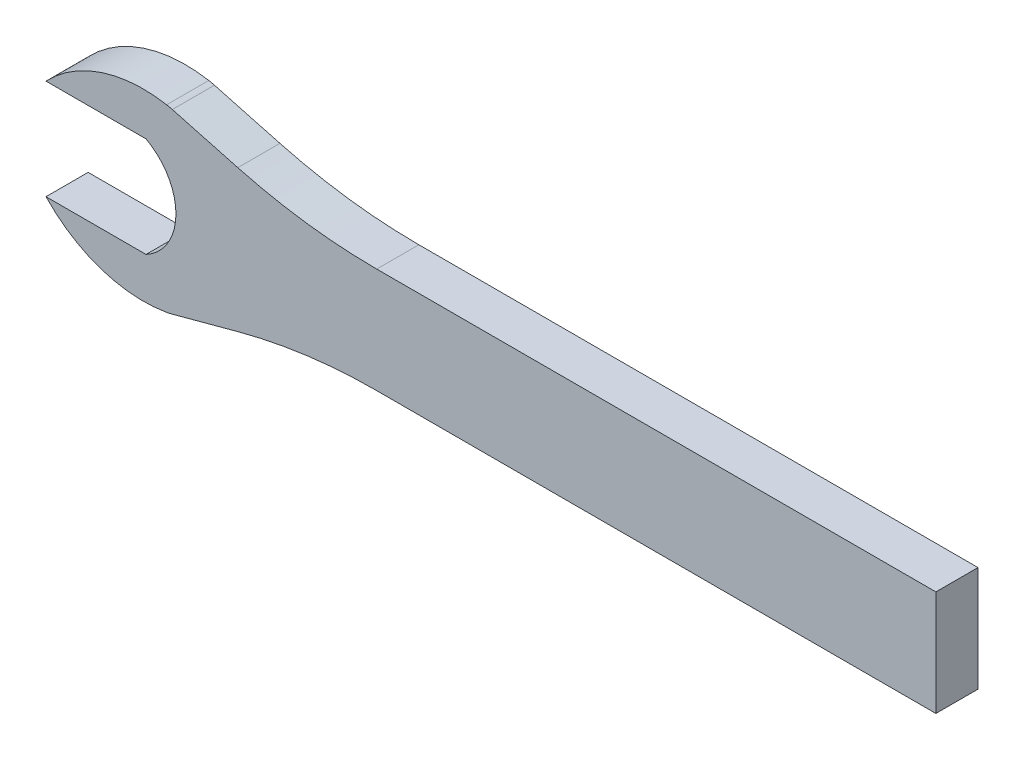
SolidWorks part; units mm, degrees
material "주조 탄소강"
ref_plane "Front Plane" through (0, 0, 0) normal (0, 0, 1) x (1, 0, 0)
ref_plane "Top Plane" through (0, 0, 0) normal (0, 1, 0) x (1, 0, 0)
ref_plane "Right Plane" through (0, 0, 0) normal (1, 0, 0) x (0, 0, -1)
ref_axis "x" through (-7.1105, 0, 0) along (1, 0, 0)
ref_axis "y" through (0, 56.4538, 0) along (0, -1, 0)
ref_axis "z" through (0, 0, -89.2869) along (0, 0, 1)
sketch "Sketch1" plane through (0, 0, 0) normal (0, 0, -1) x (1, 0, 0)
  line L0 (-19, 9.5) -> (0, 9.5)
  line L1 (0, -9.5) -> (-19, -9.5)
  line L2 (0, 0) -> (-9.5, 0) construction
  line L3 (0, 0) -> (-9.5, 0) construction
  line L4 (0, -9.5) -> (0, 9.5)
  arc A0 (0, -9.5) -> (0, 9.5) centre (-5.111, 0) ccw
  arc A1 (13.5411, 9.1333) -> (13.5411, -9.1333) centre (-10.16, 0) cw
  arc A2 (13.5411, -9.1333) -> (3.9124, -17.0708) centre (1.6906, -4.5666) cw
  arc A3 (3.9124, -17.0708) -> (-19, -9.5) centre (-0.5313, 7.9375) cw
  arc A4 (13.5411, 9.1333) -> (3.9124, 17.0708) centre (1.6906, 4.5666) ccw
  arc A5 (-19, 9.5) -> (3.9124, 17.0708) centre (-0.5313, -7.9375) cw
  dimension "D3" = 10.16
  dimension "D5" = 25.4
  dimension "D6" = 12.7
  dimension "D7" = 25.4
  dimension "D8" = 25.4
  dimension "D4" = 19
  dimension "D10" = 12.7
  dimension "D11" = 34.925
  dimension "D1" = 0
  dimension "D2" = 5.111
  dimension "D9" = 19
  dimension "D12" = 9.5
  dimension "D13" = 9.5
extrude "Boss-Extrude1" add sketch "Sketch1" along normal mid plane 8 contours L0 A5 A4 A1 A2 A3 L1 A0 region at (-8.3468, -15.7156, 0)
sketch "Sketch2" plane through (0, 0, 0) normal (0, 0, -1) x (1, 0, 0)
  line L0 (0, 0) -> (110.2756, 0) construction
  line L1 (43.8121, 10) -> (128.2047, 10)
  line L2 (133.6793, 10.2959) -> (150, 12.065)
  line L3 (150, 12.065) -> (150, -12.065)
  line L4 (17.4261, 13.4861) -> (4.9888, 16.8309)
  line L5 (133.6793, -10.2959) -> (150, -12.065)
  line L6 (43.8121, -10) -> (128.2047, -10)
  line L7 (17.4261, -13.4861) -> (4.9888, -16.8309)
  line L8 (128.2047, -10) -> (150, -10)
  line L9 (128.2047, 10) -> (150, 10)
  arc A0 (17.4261, 13.4861) -> (43.8121, 10) centre (43.8121, 111.6) ccw
  arc A1 (133.6793, 10.2959) -> (128.2047, 10) centre (128.2047, 60.8) cw
  arc A2 (133.6793, -10.2959) -> (128.2047, -10) centre (128.2047, -60.8) ccw
  arc A4 (17.4261, -13.4861) -> (43.8121, -10) centre (43.8121, -111.6) cw
  arc A7 (3.9124, -17.0708) -> (13.5411, -9.1333) centre (1.6906, -4.5666) ccw construction
  arc A9 (13.5411, 9.1333) -> (3.9124, 17.0708) centre (1.6906, 4.5666) ccw construction
  arc A10 (13.5411, -9.1333) -> (13.5411, 9.1333) centre (-10.16, 0) ccw construction
  arc A23 (3.9124, -17.0708) -> (13.5411, -9.1333) centre (1.6906, -4.5666) ccw
  arc A25 (13.5411, -9.1333) -> (13.5411, 9.1333) centre (-10.16, 0) ccw
  arc A27 (13.5411, 9.1333) -> (3.9124, 17.0708) centre (1.6906, 4.5666) ccw
  point P7 (30.3888, 10)
  point P22 (150, 0)
  point P26 (130.95, 10)
  dimension "D3" = 101.6
  dimension "D5" = 50.8
  dimension "D1" = 25.4
  dimension "D2" = 150
  dimension "D4" = 24.13
  dimension "D6" = 19.05
  dimension "D7" = 20
extrude "Boss-Extrude2" add sketch "Sketch2" along normal mid plane 8 contours A27 A25 A23 L7 A4 L6 A2 L5 L3 L2 A1 L1 A0 L4 | A25 A27 L4 A0 L1 A1 L2 L3 L5 A2 L6 A4 L7 A23 | L6 A2 L5 L3 L2 A1 L1 A0 L4 A27 A25 A23 L7 A4 region at (79.6761, 0, 0)
ref_plane "Plane1" through (0, 0, -4) normal (0, 0, 1) x (1, 0, 0)
ref_plane "Plane2" through (0, 0, 0) normal (0, 0, 1) x (1, 0, 0)
sketch "Sketch3" plane through (0, 0, 0) normal (0, 0, 1) x (1, 0, 0)
  line L0 (150, 0) -> (0, 0) construction
  circle A0 centre (150, 0) radius 15
  dimension "D2" = 30
  dimension "D1" = 150
extrude "Boss-Extrude3" [suppressed] add sketch "Sketch3" along normal mid plane 8
sketch "Sketch4" [suppressed] plane through (0, 0, 4) normal (0, 0, 1) x (0.9848, 0.1736, 0)
  line L1 (154.8352, -36.4259) -> (159.7526, -39.265)
  line L2 (159.7526, -39.265) -> (165.4309, -39.265)
  line L3 (165.4309, -39.265) -> (170.3484, -36.4259)
  line L4 (170.3484, -36.4259) -> (173.1875, -31.5084)
  line L5 (173.1875, -31.5084) -> (173.1875, -25.8302)
  line L6 (173.1875, -25.8302) -> (170.3484, -20.9127)
  line L7 (170.3484, -20.9127) -> (165.4309, -18.0736)
  line L8 (165.4309, -18.0736) -> (159.7526, -18.0736)
  line L9 (159.7526, -18.0736) -> (154.8352, -20.9127)
  line L10 (154.8352, -20.9127) -> (151.996, -25.8302)
  line L11 (151.996, -25.8302) -> (151.996, -31.5084)
  line L12 (151.996, -31.5084) -> (154.8352, -36.4259)
  circle A0 centre (162.5918, -28.6693) radius 15 construction
  circle A1 centre (162.5918, -28.6693) radius 10.9695 construction
  dimension "D1" = 21.939
extrude "Cut-Extrude1" [suppressed] cut sketch "Sketch4" against normal through all
sketch "Sketch5" plane through (0, 0, 4) normal (0, 0, 1) x (1, 0, 0)
  line L0 (31.75, 0) -> (133.35, 0) construction
  line L1 (31.75, 4.1275) -> (133.35, 4.1275)
  line L2 (31.75, -4.1275) -> (133.35, -4.1275)
  arc A0 (31.75, 4.1275) -> (31.75, -4.1275) centre (31.75, 0) ccw
  arc A1 (133.35, -4.1275) -> (133.35, 4.1275) centre (133.35, 0) ccw
  point P2 (82.55, 0)
  dimension "D1" = 101.6
  dimension "D2" = 8.255
  dimension "D3" = 31.75
extrude "Cut-Extrude2" [suppressed] cut sketch "Sketch5" against normal blind 0.762
mirror "Mirror1" [suppressed] about plane through (0, 0, 0) normal (0, 0, 1)
fillet "Fillet2" [suppressed] radius 0.762
fillet "Fillet3" [suppressed] radius 1.27
fillet "Fillet4" [suppressed] radius 0.381 tangent propagation no
sketch "Sketch6" [suppressed] plane through (0, 0, 1.4605) normal (0, 0, 1) x (1, 0, 0)
  text T0 "5/8"
  dimension "D1" = 33.655
  dimension "D2" = 1.905
extrude "Boss-Extrude4" [suppressed] add sketch "Sketch6" along normal blind 0.381
sketch "Sketch7" [suppressed] plane through (0, 0, 1.4605) normal (0, 0, 1) x (1, 0, 0)
  text T0 "SPANNER" font "Century Gothic" height in points 14
  dimension "D1" = 69.85
  dimension "D2" = 1.905
extrude "Boss-Extrude5" [suppressed] add sketch "Sketch7" along normal blind 0.381
